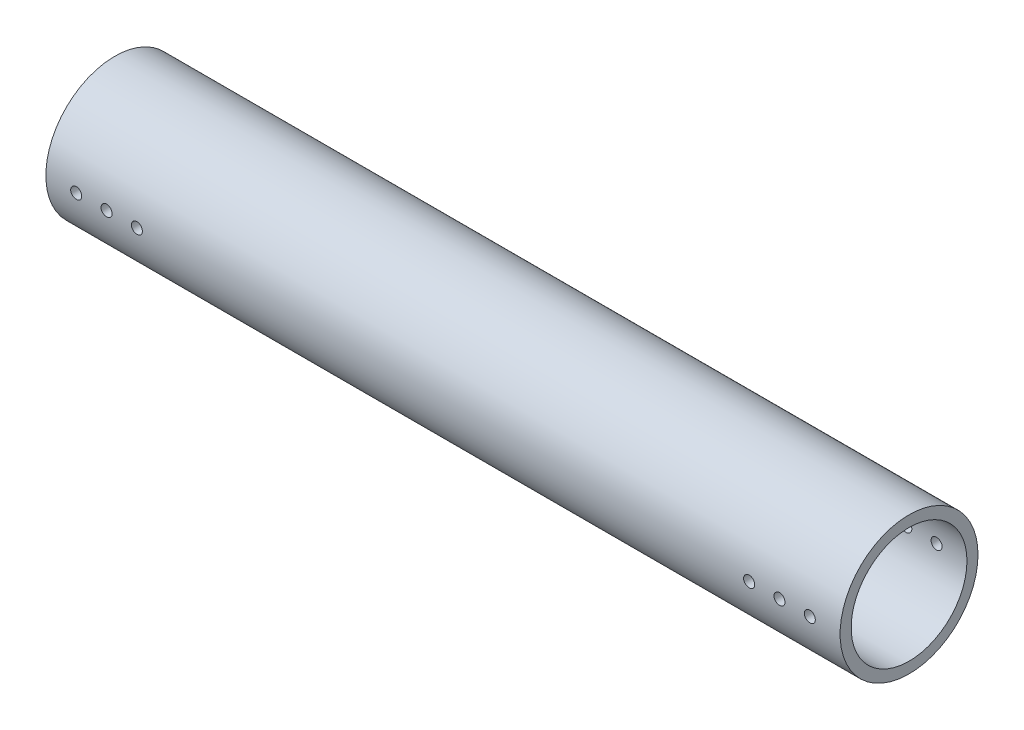
SolidWorks part; units mm, degrees
material "Zoltek Panex 33"
ref_plane "Спереди" through (0, 0, 0) normal (0, 0, 1) x (1, 0, 0)
ref_plane "Сверху" through (0, 0, 0) normal (0, 1, 0) x (1, 0, 0)
ref_plane "Справа" through (0, 0, 0) normal (1, 0, 0) x (0, 0, -1)
other "Configuration Table"
sketch "Эскиз2" plane through (0, 0, 0) normal (1, 0, 0) x (0, 0, -1)
  circle A0 centre (0, 0) radius 25
  circle A1 centre (0, 0) radius 21
  dimension "D1" = 50
  dimension "D2" = 42
extrude "Бобышка-Вытянуть2" add sketch "Эскиз2" along normal blind 288
ref_plane "Плоскость1" through (0, 0, 25) normal (0, 0, 1) x (1, 0, 0)
sketch "Эскиз4" plane through (0, 0, 25) normal (0, 0, 1) x (1, 0, 0)
  line L0 (0, -25) -> (288, -25) construction
  line L1 (288, -25) -> (288, 25) construction
  circle A0 centre (11, 0) radius 2
  circle A1 centre (277, 0) radius 2
  circle A2 centre (22, 0) radius 2
  circle A3 centre (33, 0) radius 2
  circle A4 centre (266, 0) radius 2
  circle A5 centre (255, 0) radius 2
  dimension "D1" = 4
  dimension "D4" = 4
  dimension "D6" = 4
  dimension "D8" = 4
  dimension "D10" = 4
  dimension "D11" = 4
  dimension "D2" = 11
  dimension "D3" = 25
  dimension "D5" = 11
  dimension "D7" = 11
  dimension "D9" = 11
  dimension "15" = 11
  dimension "D12" = 11
extrude "Вырез-Вытянуть2" cut sketch "Эскиз4" against normal through all and the other way blind 10 contours A0 | A1 | A2 | A3 | A5 | A4
equation "\"Diameter\"= 50мм"
equation "\"D1@Эскиз2\"= \"Diameter\""
equation "\"Length\"= 288мм"
equation "\"Thickness\"= 4мм"
equation "\"D1@Бобышка-Вытянуть2\"= \"Length\""
equation "\"D2@Эскиз2\" = \"Diameter\" - \"Thickness\" * 2"
equation "\"D4@Эскиз4\"=\"D1@Эскиз4\""
equation "\"D5@Эскиз4\"=\"D2@Эскиз4\""
equation "\"D3@Эскиз4\"=\"Diameter\"/2"
equation "\"D6@Эскиз4\"=\"D1@Эскиз4\""
equation "\"D8@Эскиз4\"=\"D6@Эскиз4\""
equation "\"D10@Эскиз4\"=\"D4@Эскиз4\""
equation "\"D11@Эскиз4\"=\"D4@Эскиз4\""
equation "\"D7@Эскиз4\"=\"D2@Эскиз4\""
equation "\"D9@Эскиз4\"=\"D2@Эскиз4\""
equation "\"D12@Эскиз4\"=\"D2@Эскиз4\""
equation "\"15@Эскиз4\"=\"D2@Эскиз4\""
